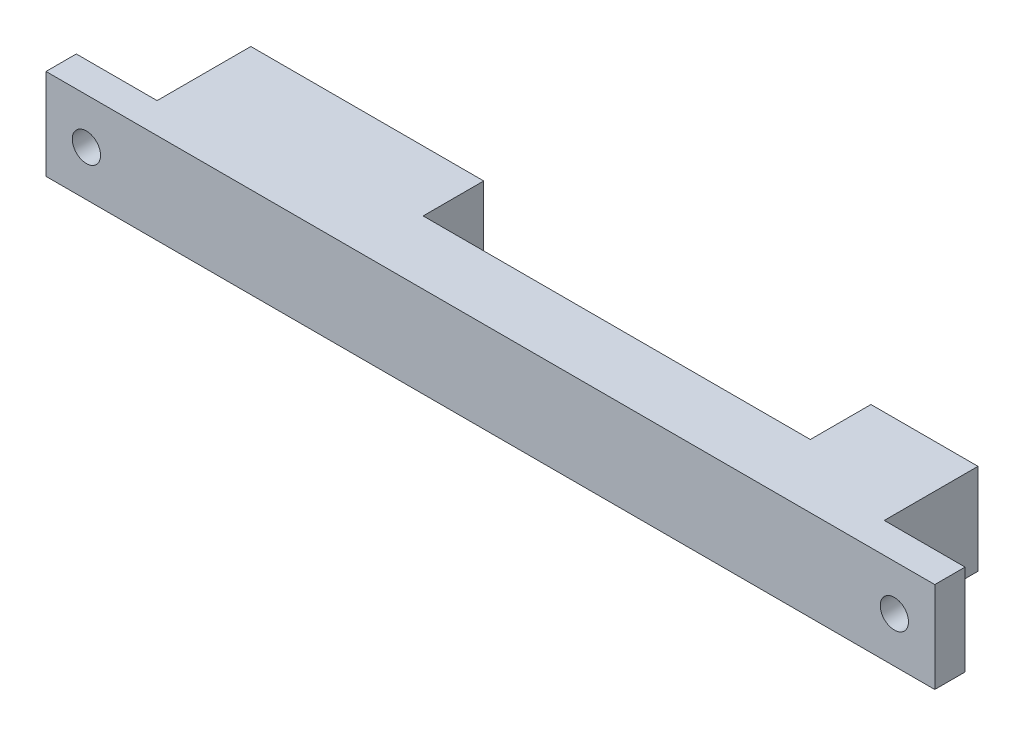
SolidWorks part; units mm, degrees
ref_plane "Front Plane" through (0, 0, 0) normal (0, 0, 1) x (1, 0, 0)
ref_plane "Top Plane" through (0, 0, 0) normal (0, 1, 0) x (1, 0, 0)
ref_plane "Right Plane" through (0, 0, 0) normal (1, 0, 0) x (0, 0, -1)
sketch "Sketch1" plane through (0, 0, 0) normal (0, 0, 1) x (1, 0, 0)
  line L1 (-36, 28.4) -> (36, 28.4)
  line L2 (-36, 28.4) -> (-36, 19.4)
  line L3 (-36, 19.4) -> (36, 19.4)
  line L4 (36, 28.4) -> (36, 19.4)
  line L12 (-12.94, 20.4) -> (-12.94, 27.4)
  line L13 (-12.94, 19.4) -> (-12.94, 28.4)
  line L14 (35, 28.4) -> (35, 7) construction
  line L15 (25.4, 20.4) -> (25.4, 27.4)
  line L16 (25.4, 19.4) -> (25.4, 28.4)
  line L17 (-35, 28.4) -> (-35, 7) construction
  line L19 (-35, 28.4) -> (35, 28.4) construction
  circle A0 centre (32, 23.9) radius 1.4 construction
  circle A1 centre (32, 23.9) radius 1.4 construction
  circle A2 centre (-32, 23.9) radius 1.4 construction
  circle A3 centre (-32, 23.9) radius 1.4 construction
  circle A4 centre (-32, 23.9) radius 2.1
  circle A5 centre (32, 23.9) radius 2.1
  dimension "D6" = 4.2
  dimension "D1" = 9
  dimension "D4" = 1
  dimension "D5" = 1
  dimension "D2" = 1
  dimension "D3" = 1
extrude "Boss-Extrude1" add sketch "Sketch1" along normal up to surface (12.281 mm away) contours A5 | L16 L3 L4 L1 A5 | L3 L13 L1 L2 A4 | A4 | L3 L16 L1 L13 region at (-23.9314, 23.9, 0) region at (6.23, 23.9, 0) region at (30.7, 28.2609, 0) region at (-32, 23.9, 0) region at (32, 23.9, 0)
extrude "Cut-Extrude1" cut sketch "Sketch1<3>" along normal blind 6 contours L3 L16 L1 L13 region at (6.23, 23.9, 0)
sketch "Sketch1<3>" plane through (0, 0, 0) normal (0, 0, 1) x (1, 0, 0) same geometry as "Sketch1"
extrude "Cut-Extrude2" cut sketch "Sketch1<4>" along normal blind 4.5 contours A4 | A5 region at (-32, 23.9, 0) region at (32, 23.9, 0)
sketch "Sketch1<4>" plane through (0, 0, 0) normal (0, 0, 1) x (1, 0, 0) same geometry as "Sketch1"
sketch "Sketch2" plane through (0, 0, 12.281) normal (0, 0, 1) x (1, 0, 0)
  line L0 (36, 19.4) -> (36, 28.4)
  line L1 (36, 19.4) -> (44, 19.4)
  line L2 (36, 28.4) -> (44, 28.4)
  line L3 (44, 19.4) -> (44, 28.4)
  line L4 (-36, 19.4) -> (-36, 28.4)
  line L5 (-36, 19.4) -> (-44, 19.4)
  line L6 (-36, 28.4) -> (-44, 28.4)
  line L7 (-44, 19.4) -> (-44, 28.4)
  line L8 (-44, 19.4) -> (-36, 28.4) construction
  line L9 (36, 19.4) -> (44, 28.4) construction
  circle A0 centre (-40, 23.9) radius 1.4
  circle A1 centre (40, 23.9) radius 1.4
  line M9 (-36, 28.4) -> (-36, 19.4)
  line M11 (36, 19.4) -> (36, 28.4)
  dimension "D2" = 2.8
  dimension "D1" = 8
extrude "Boss-Extrude2" add sketch "Sketch2" against normal blind 3 contours L7 L5 L6 A0 M9 | L1 L3 L2 A1 M11 region at (36.1204, 23.9, 12.281) region at (-40, 19.5204, 12.281)
